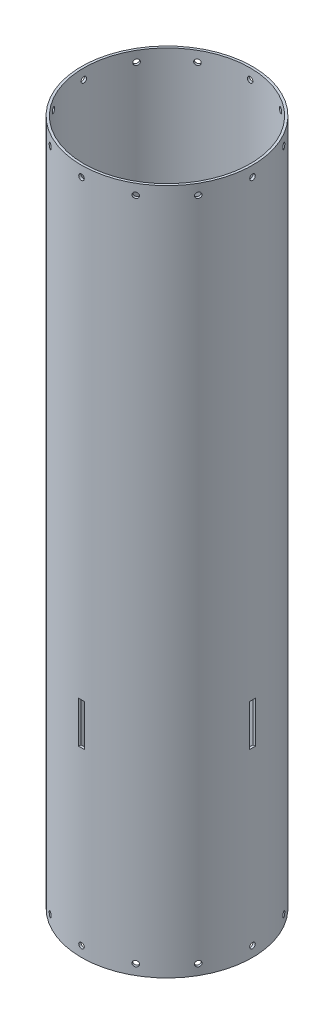
SolidWorks part; units mm, degrees
material "Fiberglass"
ref_plane "Front Plane" through (0, 0, 0) normal (0, 0, 1) x (1, 0, 0)
ref_plane "Top Plane" through (0, 0, 0) normal (0, 1, 0) x (1, 0, 0)
ref_plane "Right Plane" through (0, 0, 0) normal (1, 0, 0) x (0, 0, -1)
sketch "Sketch1" plane through (0, 0, 0) normal (0, 1, 0) x (1, 0, 0)
  circle A0 centre (0, 0) radius 76.2
  circle A1 centre (0, 0) radius 78.359
  dimension "D1" = 152.4
  dimension "D2" = 156.718
extrude "Boss-Extrude1" add sketch "Sketch1" along normal blind 628.65
sketch "Sketch2" plane through (0, 0, 0) normal (0, 0, 1) x (1, 0, 0)
  line L0 (0, 0) -> (0, 105.6712) construction
  line L1 (-76.2, 0) -> (76.2, 0) construction
  line L2 (-78.359, 0) -> (78.359, 0) construction
  line L3 (78.359, 314.325) -> (42.8908, 314.325) construction
  line L4 (78.359, 0) -> (78.359, 628.65) construction
  circle A0 centre (0, 9.525) radius 2.54
  circle A1 centre (0, 619.125) radius 2.54
  dimension "D1" = 5.08
  dimension "D2" = 9.525
extrude "Cut-Extrude1" cut sketch "Sketch2" against normal through all
ref_axis "Axis1" through (0, 0, 0) along (0, 1, 0)
pattern_circular "CirPattern1" count 12 over 360 about axis through (0, 0, 0) along (0, 1, 0) of "Cut-Extrude1" reverse direction yes
sketch "Sketch3" plane through (0, 0, 0) normal (0, 0, 1) x (1, 0, 0)
  line L0 (0, 0) -> (0, 105.6712) construction
  line L1 (-2.54, 166.37) -> (2.54, 166.37)
  line L2 (-2.54, 166.37) -> (-2.54, 204.47)
  line L3 (-2.54, 204.47) -> (2.54, 204.47)
  line L4 (2.54, 166.37) -> (2.54, 204.47)
  line L5 (-2.54, 166.37) -> (2.54, 204.47) construction
  line L6 (-2.54, 204.47) -> (2.54, 166.37) construction
  line L7 (-76.2, 0) -> (76.2, 0) construction
  line L8 (0, 628.65) -> (0, 408.1695) construction
  line L9 (76.2, 628.65) -> (-76.2, 628.65) construction
  point P0 (0, 185.42)
  dimension "D1" = 166.37
  dimension "D2" = 38.1
  dimension "D3" = 5.08
extrude "Cut-Extrude2" cut sketch "Sketch3" against normal through all
ref_axis "Axis2" through (0, 628.65, 0) along (0, -1, 0)
pattern_circular "CirPattern2" count 4 over 360 about axis through (0, 628.65, 0) along (0, -1, 0) of "Cut-Extrude2"
